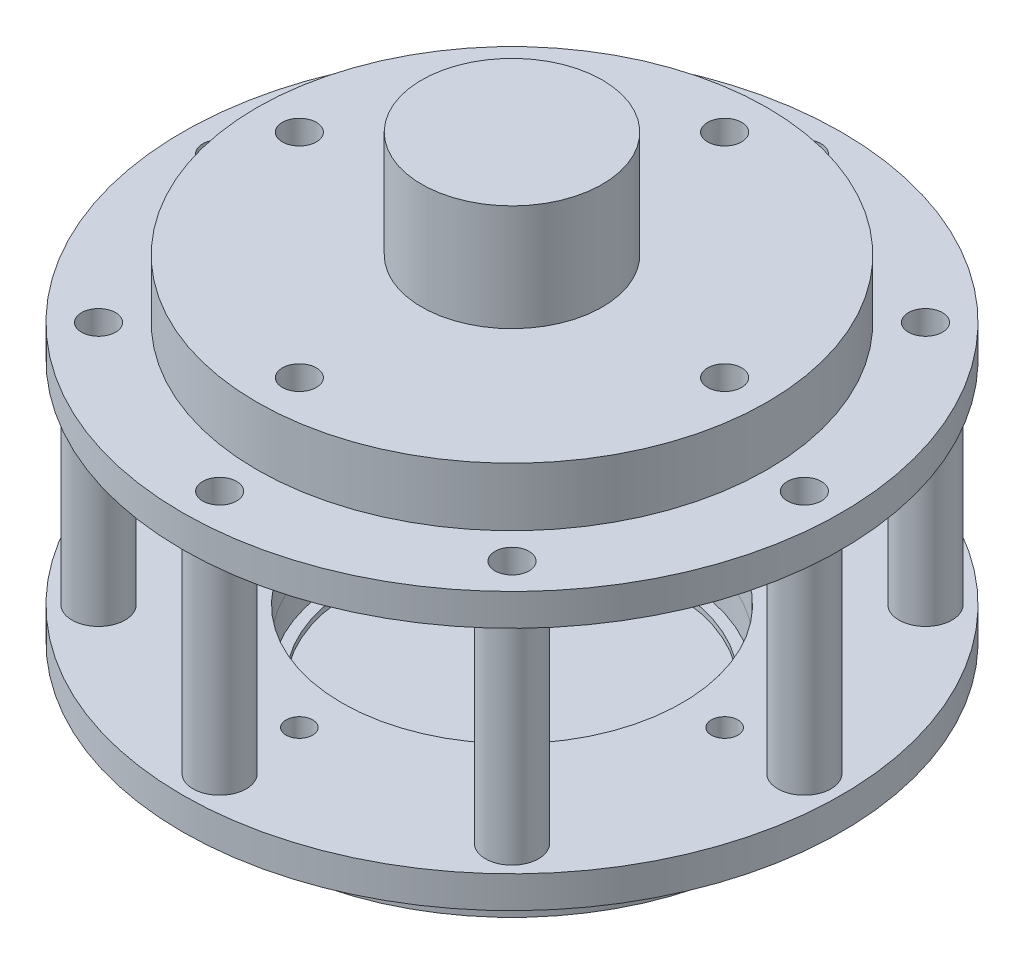
SolidWorks part; units mm, degrees
ref_plane "正面" through (0, 0, 0) normal (0, 0, 1) x (1, 0, 0)
ref_plane "平面" through (0, 0, 0) normal (0, 1, 0) x (1, 0, 0)
ref_plane "右側面" through (0, 0, 0) normal (1, 0, 0) x (0, 0, -1)
sketch "ｽｹｯﾁ1" plane through (0, 0, 0) normal (0, 1, 0) x (1, 0, 0)
  circle A0 centre (0, 0) radius 31
  circle A1 centre (0, 0) radius 27.5 construction
  circle A2 centre (0, 27.5) radius 1.6
  circle A3 centre (19.4454, 19.4454) radius 1.6
  circle A4 centre (27.5, 0) radius 1.6
  circle A5 centre (19.4454, -19.4454) radius 1.6
  circle A6 centre (0, -27.5) radius 1.6
  circle A7 centre (-19.4454, -19.4454) radius 1.6
  circle A8 centre (-27.5, 0) radius 1.6
  circle A9 centre (-19.4454, 19.4454) radius 1.6
  circle A10 centre (0, 0) radius 16
  circle A11 centre (0, 0) radius 20 construction
  circle A12 centre (20, 0) radius 1.25
  circle A13 centre (0, -20) radius 1.25
  circle A14 centre (-20, 0) radius 1.25
  circle A15 centre (0, 20) radius 1.25
  point P22 (0, 0)
  point P25 (-4.3108, -41.1604)
  point P26 (0, 0)
  point P33 (0, 0)
  dimension "D1" = 55
  dimension "D2" = 62
  dimension "D3" = 3.2
  dimension "D5" = 32
  dimension "D6" = 40
  dimension "D7" = 2.5
  dimension "D4" = 8
  dimension "D8" = 4
extrude "ﾎﾞｽ - 押し出し1" add sketch "ｽｹｯﾁ1" along normal blind 3
sketch "ｽｹｯﾁ2" plane through (0, 3, 0) normal (0, 1, 0) x (1, 0, 0)
  circle A0 centre (0, 27.5) radius 2.5
  circle A1 centre (19.4454, 19.4454) radius 2.5
  circle A2 centre (27.5, 0) radius 2.5
  circle A3 centre (19.4454, -19.4454) radius 2.5
  circle A4 centre (0, -27.5) radius 2.5
  circle A5 centre (-19.4454, -19.4454) radius 2.5
  circle A6 centre (-27.5, 0) radius 2.5
  circle A7 centre (-19.4454, 19.4454) radius 2.5
  circle A8 centre (-19.4454, 19.4454) radius 1.6 construction
  point P4 (0, 0)
  point P19 (0, 0)
  dimension "D1" = 5
  dimension "D2" = 8
extrude "ｶｯﾄ - 押し出し1" cut sketch "ｽｹｯﾁ2" against normal blind 0.5
sketch "ｽｹｯﾁ3" plane through (0, 2.5, 0) normal (0, 1, 0) x (1, 0, 0)
  circle A1 centre (-27.5, 0) radius 2.5 construction
  circle A3 centre (-27.5, 0) radius 2.5
  circle A4 centre (-27.5, 0) radius 1.25
  circle A6 centre (-19.4454, 19.4454) radius 2.5
  circle A7 centre (-19.4454, 19.4454) radius 1.25
  circle A8 centre (0, 27.5) radius 2.5
  circle A9 centre (0, 27.5) radius 1.25
  circle A10 centre (19.4454, 19.4454) radius 2.5
  circle A11 centre (19.4454, 19.4454) radius 1.25
  circle A12 centre (27.5, 0) radius 2.5
  circle A13 centre (27.5, 0) radius 1.25
  circle A14 centre (19.4454, -19.4454) radius 2.5
  circle A15 centre (19.4454, -19.4454) radius 1.25
  circle A16 centre (0, -27.5) radius 2.5
  circle A17 centre (0, -27.5) radius 1.25
  circle A18 centre (-19.4454, -19.4454) radius 2.5
  circle A19 centre (-19.4454, -19.4454) radius 1.25
  circle A20 centre (-19.4454, 19.4454) radius 1.6 construction
  point P1 (-21.6074, 19.4454)
  point P29 (0, 0)
  dimension "D1" = 2.5
  dimension "D2" = 8
extrude "ﾎﾞｽ - 押し出し2" add sketch "ｽｹｯﾁ3" along normal blind 21 separate body
sketch "ｽｹｯﾁ4" plane through (0, 0, 0) normal (0, -1, 0) x (1, 0, 0)
  circle A0 centre (0, 0) radius 24
  circle A1 centre (20, 0) radius 1.6
  circle A2 centre (0, -20) radius 1.6
  circle A3 centre (-20, 0) radius 1.6
  circle A4 centre (0, 20) radius 1.6
  circle A5 centre (0, 20) radius 1.25 construction
  circle A6 centre (0, 0) radius 16 construction
  circle A7 centre (0, 0) radius 16
  point P6 (15.8644, 29.5109)
  point P15 (0, 0)
  dimension "D1" = 48
  dimension "D2" = 3.2
  dimension "D3" = 4
extrude "ﾎﾞｽ - 押し出し3" add sketch "ｽｹｯﾁ4" along normal blind 3 separate body
sketch "ｽｹｯﾁ5" plane through (0, -3, 0) normal (0, -1, 0) x (1, 0, 0)
  circle A0 centre (0, 0) radius 24
  circle A1 centre (0, 0) radius 15
  circle A2 centre (0, 0) radius 24 construction
  circle A3 centre (0, 0) radius 16 construction
  circle A5 centre (20, 0) radius 1.6
  circle A6 centre (20, 0) radius 1.6 construction
  circle A7 centre (0, -20) radius 1.6
  circle A8 centre (-20, 0) radius 1.6
  circle A9 centre (0, 20) radius 1.6
  point P8 (0, 0)
  point P23 (0, 0)
  dimension "D1" = 1
  dimension "D2" = 4
extrude "ﾎﾞｽ - 押し出し4" add sketch "ｽｹｯﾁ5" along normal blind 0.5 separate body
sketch "ｽｹｯﾁ6" plane through (0, -3.5, 0) normal (0, -1, 0) x (1, 0, 0)
  circle A0 centre (0, 0) radius 24
  circle A1 centre (0, 20) radius 1.6 construction
  circle A2 centre (20, 0) radius 1.6 construction
  circle A3 centre (0, -20) radius 1.6 construction
  circle A4 centre (0, 20) radius 1.6
  circle A5 centre (20, 0) radius 1.6
  circle A6 centre (0, -20) radius 1.6
  circle A7 centre (-20, 0) radius 1.6 construction
  circle A8 centre (-20, 0) radius 1.6
  circle A9 centre (0, 0) radius 24 construction
extrude "ﾎﾞｽ - 押し出し5" add sketch "ｽｹｯﾁ6" along normal blind 2 separate body
sketch "ｽｹｯﾁ7" plane through (0, -5.5, 0) normal (0, -1, 0) x (1, 0, 0)
  circle A0 centre (0, 0) radius 8.5
  dimension "D1" = 17
extrude "ﾎﾞｽ - 押し出し6" add sketch "ｽｹｯﾁ7" along normal blind 10 separate body
ref_plane "平面1" through (0, 13, 0) normal (0, 1, 0) x (1, 0, 0)
mirror "ﾐﾗｰ1" about plane through (0, 13, 0) normal (0, 1, 0) of bodies 102
ref_plane "平面2" through (0, 13, 0) normal (0, 1, 0) x (1, 0, 0)
combine bodies "組み合わせ1" operation type add bodies to combine 114 113 112
mirror "ﾐﾗｰ2" about plane through (0, 13, 0) normal (0, 1, 0) of bodies 116 115
